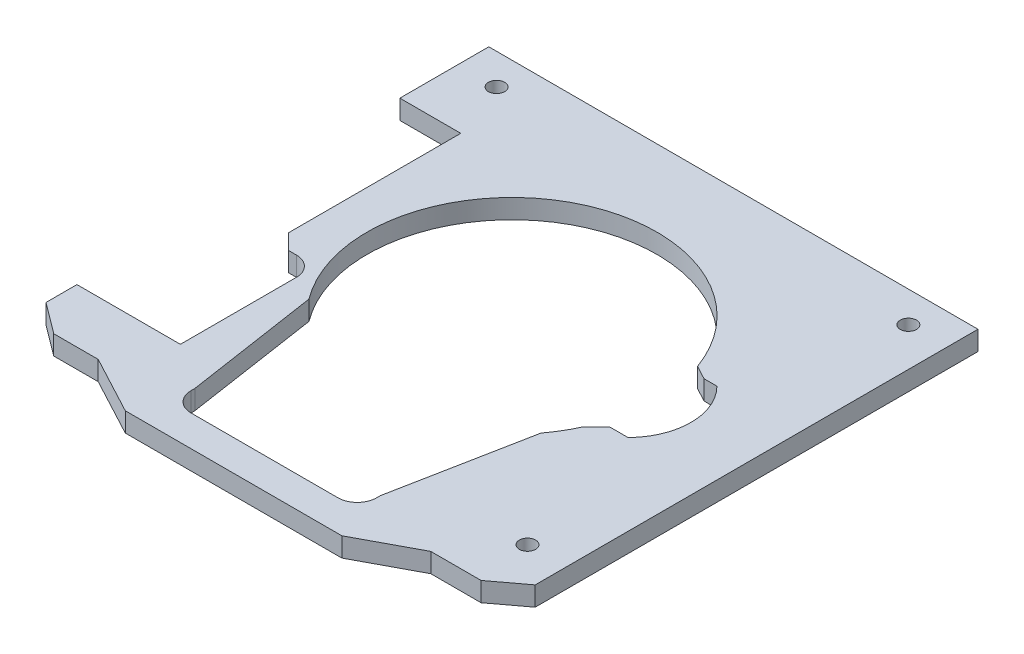
SolidWorks part; units mm, degrees
ref_plane "Спереди" through (0, 0, 0) normal (0, 0, 1) x (1, 0, 0)
ref_plane "Сверху" through (0, 0, 0) normal (0, 1, 0) x (1, 0, 0)
ref_plane "Справа" through (0, 0, 0) normal (1, 0, 0) x (0, 0, -1)
ref_plane "Плоскость4" through (0, 249.196, 0) normal (0, 1, 0) x (1, 0, 0)
sketch "Эскиз1" plane through (0, 249.196, 0) normal (0, 1, 0) x (1, 0, 0)
  line L1 (128.059, -60.5) -> (128.059, 60.5) construction
  line L2 (128.059, -32.2731) -> (108.059, -32.2731) construction
  line L4 (108.059, -146.7731) -> (128.059, -146.7731) construction
  line L10 (1.559, 34.1) -> (1.559, -34.1) construction
  line L11 (1.559, -146.7731) -> (40.059, -146.7731)
  line L12 (128.059, -32.2731) -> (128.059, -55.2731)
  line L14 (1.559, -55.2731) -> (1.559, -32.2731)
  line L15 (1.559, -146.7731) -> (1.559, -138.7731)
  line L16 (128.059, -32.2731) -> (107.059, -32.2731)
  line L17 (100.2517, -101.7731) -> (107.059, -101.7731)
  line L19 (100.2517, -146.7731) -> (88.059, -146.7731)
  line L21 (88.059, -146.7731) -> (88.059, -152.7731)
  line L22 (88.059, -152.7731) -> (40.059, -152.7731)
  line L23 (40.059, -152.7731) -> (40.059, -146.7731)
  line L24 (100.7359, -78.7758) -> (107.059, -78.7758)
  line L25 (88.059, -160.7731) -> (92.059, -160.7731)
  line L28 (107.059, -152.7731) -> (92.059, -160.7731)
  line L29 (107.059, -152.7731) -> (120.059, -152.7731)
  line L30 (120.059, -152.7731) -> (128.059, -146.7731)
  line L31 (17.309, -103.7731) -> (28.309, -103.7731)
  line L32 (17.309, -89.5231) -> (17.309, -55.2731)
  line L33 (88.059, -160.7731) -> (40.059, -160.7731)
  line L34 (40.059, -160.7731) -> (36.059, -160.7731)
  line L35 (17.309, -103.7731) -> (17.309, -89.5231)
  line L36 (100.2517, -101.7731) -> (100.2517, -146.7731)
  line L37 (21.059, -152.7731) -> (9.559, -152.7731)
  line L38 (1.559, -146.7731) -> (9.559, -152.7731)
  line L39 (21.059, -152.7731) -> (36.059, -160.7731)
  line L40 (17.309, -55.2731) -> (1.559, -55.2731)
  line L41 (28.309, -138.7731) -> (28.309, -103.7731)
  line L42 (1.559, -55.2731) -> (1.559, -32.2731)
  line L43 (28.309, -138.7731) -> (1.559, -138.7731)
  line L44 (100.7359, -78.7758) -> (100.7359, -32.2731)
  line L45 (100.7359, -32.2731) -> (128.059, -32.2731)
  line L46 (100.7359, -32.2731) -> (1.559, -32.2731)
  line L47 (88.059, -160.7731) -> (88.059, -152.7731)
  line L48 (128.059, -32.2731) -> (128.059, -146.7731)
  line L50 (34.809, -64.5231) -> (34.809, -114.5231) construction
  line L51 (34.809, -112.0231) -> (40.059, -146.7731)
  line L54 (94.809, -64.5231) -> (94.809, -114.5231) construction
  line L55 (94.809, -112.0231) -> (88.059, -146.7731)
  circle A0 centre (64.809, -89.5231) radius 37.5
  arc A1 (49.5385, -55.2731) -> (80.0795, -55.2731) centre (64.809, -89.5231) cw
  arc A2 (80.0795, -55.2731) -> (100.7359, -78.7758) centre (64.809, -89.5231) cw
  circle A3 centre (118.059, -138.7731) radius 2.1
  circle A4 centre (118.059, -40.2731) radius 2.1
  circle A5 centre (11.559, -40.2731) radius 2.1
  arc A6 (107.059, -78.7758) -> (107.059, -101.7731) centre (95.5603, -90.2744) cw
  arc A7 (34.809, -112.0231) -> (94.809, -112.0231) centre (64.809, -89.5231) ccw
extrude "Бобышка-Вытянуть3" add sketch "Эскиз1" along normal blind 5 contours A0 L55 L19 L36 | A0 L44 L46 L14 L40 L32 L35 L31 L41 L43 L15 L11 L51 A5 | L33 L47 L22 L23 L11 L38 L37 L39 L34 | L24 A6 L17 L36 L19 L21 L47 L25 L28 L29 L30 L48 L12 L16 L45 L44 A4 A3 region at (3.0738, 249.196, 142.7731) region at (47.4166, 249.196, 154.4993) region at (113.7514, 249.196, 95.6571) region at (95.8427, 249.196, 129.9353)
fillet "Скругление1" radius 5 3 edges at (28.309, 251.696, 103.7731) (40.059, 251.696, 152.7731) (88.059, 251.696, 152.7731)
chamfer "Фаска1" distance 2 angle 45 2 edges at (100.2517, 251.696, 101.7731) (100.7359, 251.696, 78.7758) first distance on face at (103.6553, 251.696, 101.7731) first distance on face at (57.8478, 251.696, 75.7197)
chamfer "Фаска2" distance 4 angle 45 1 edges at (17.309, 251.696, 103.7731)
